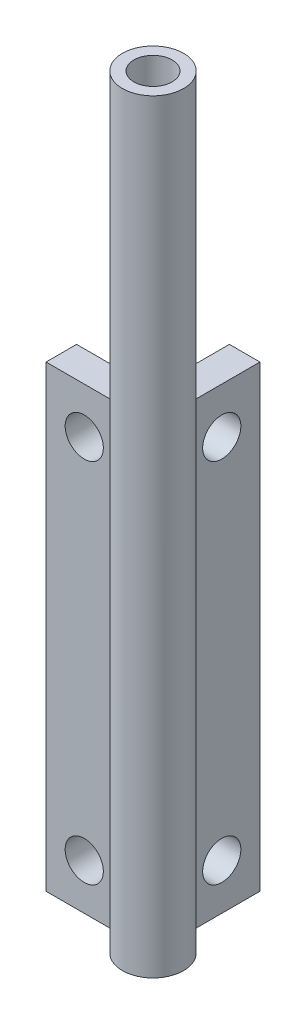
SolidWorks part; units mm, degrees
ref_plane "Front Plane" through (0, 0, 0) normal (0, 0, 1) x (1, 0, 0)
ref_plane "Top Plane" through (0, 0, 0) normal (0, 1, 0) x (1, 0, 0)
ref_plane "Right Plane" through (0, 0, 0) normal (1, 0, 0) x (0, 0, -1)
sketch "Sketch1" plane through (0, 0, 0) normal (0, 1, 0) x (1, 0, 0)
  circle A0 centre (0, 0) radius 5.08
  dimension "D1" = 10.16
extrude "Boss-Extrude1" add sketch "Sketch1" along normal blind 127
sketch "Sketch2" plane through (0, 0, 0) normal (0, -1, 0) x (1, 0, 0)
  circle A0 centre (0, 0) radius 3.175
  dimension "D1" = 6.35
extrude "Cut-Extrude1" cut sketch "Sketch2" against normal through all
sketch "Sketch11" plane through (0, 0, 0) normal (0, -1, 0) x (1, 0, 0)
  line L0 (0, 0) -> (-5.08, 0) construction
  line L1 (0, 0) -> (0, -5.08) construction
  line L2 (0, 0) -> (3.175, 0) construction
  line L3 (0, 0) -> (0, 3.175) construction
  line L8 (0, -17.78) -> (0, -5.08)
  line L13 (-17.78, 0) -> (-5.08, 0)
  line L14 (0, -17.78) -> (-5.08, -17.78)
  line L15 (-5.08, -17.78) -> (-5.08, -5.08)
  line L16 (-5.08, -5.08) -> (-17.78, -5.08)
  line L17 (-17.78, -5.08) -> (-17.78, 0)
  line L18 (0, -5.08) -> (0, -3.175)
  line L19 (-5.08, 0) -> (-3.175, 0)
  circle A0 centre (0, 0) radius 5.08 construction
  circle A1 centre (0, 0) radius 3.175 construction
  arc A5 (-3.175, 0) -> (0, -3.175) centre (0, 0) ccw
  point P13 (-17.78, -5.08)
  point P19 (-17.78, -5.08)
  point P22 (-5.08, -5.08)
  point P23 (0, 0)
  point P24 (0, 0)
  point P25 (0, 0)
  point P26 (0, 0)
  dimension "D1" = 12.7
  dimension "D2" = 90
  dimension "D3" = 5.08
extrude "Boss-Extrude5" add sketch "Sketch11" against normal blind 76.2
sketch "Sketch12" plane through (0, 0, 0) normal (1, 0, 0) x (0, 0, -1)
  line L0 (17.78, 76.2) -> (17.78, 0) construction
  line L1 (17.78, 0) -> (5.08, 0) construction
  circle A0 centre (11.43, 7.62) radius 3.175
  dimension "D1" = 6.35
  dimension "D2" = 6.35
  dimension "D3" = 7.62
extrude "Cut-Extrude7" cut sketch "Sketch12" against normal up to next
sketch "Sketch13" plane through (0, 0, 0) normal (0, 0, 1) x (1, 0, 0)
  line L0 (-5.08, 0) -> (-17.78, 0) construction
  line L1 (-17.78, 76.2) -> (-17.78, 0) construction
  circle A0 centre (-11.43, 7.62) radius 3.175
  dimension "D1" = 6.35
  dimension "D2" = 7.62
  dimension "D3" = 6.35
extrude "Cut-Extrude8" cut sketch "Sketch13" against normal up to next
ref_plane "Plane6" through (0, 38.1, 0) normal (0, -1, 0) x (-1, 0, 0)
mirror "Mirror4" about plane through (0, 38.1, 0) normal (0, -1, 0) of "Cut-Extrude8", "Cut-Extrude7"
